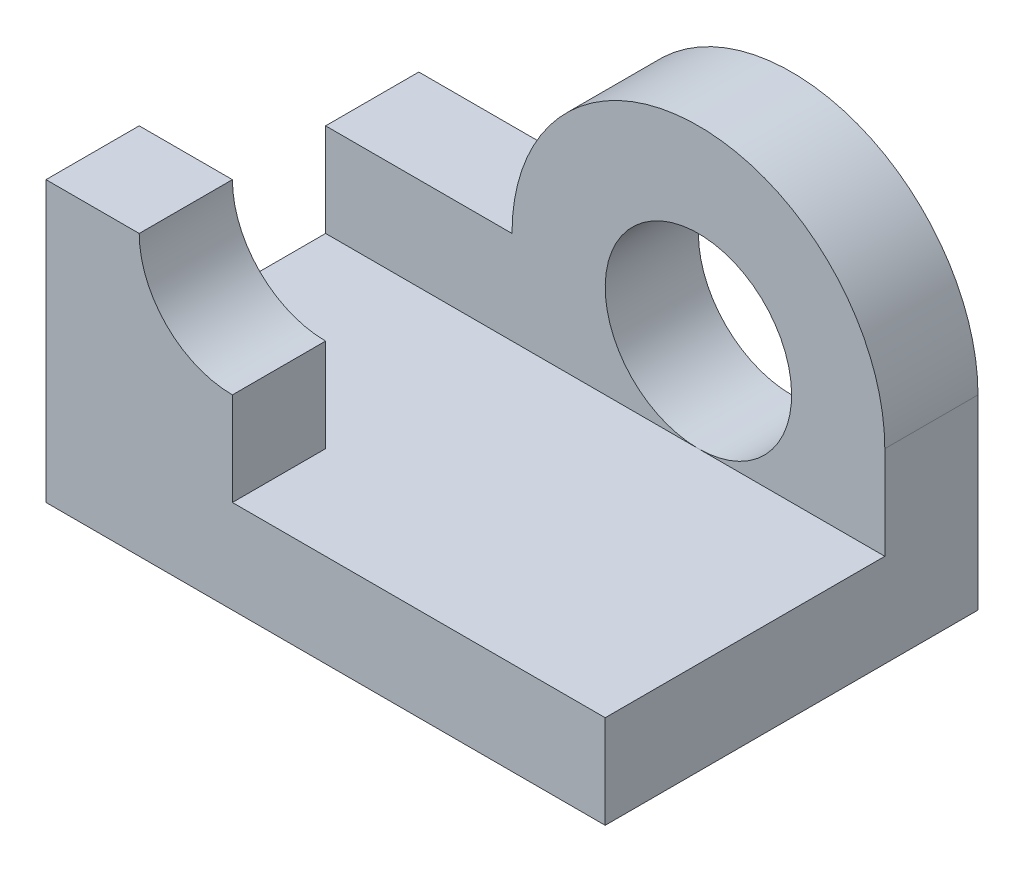
SolidWorks part; units mm, degrees
ref_plane "Front Plane" through (0, 0, 0) normal (0, 0, 1) x (1, 0, 0)
ref_plane "Top Plane" through (0, 0, 0) normal (0, 1, 0) x (1, 0, 0)
ref_plane "Right Plane" through (0, 0, 0) normal (1, 0, 0) x (0, 0, -1)
sketch "Sketch1" plane through (0, 0, 0) normal (0, 0, 1) x (1, 0, 0)
  line L0 (0, 0) -> (0, 762)
  line L1 (0, 762) -> (254, 762)
  line L2 (508, 508) -> (508, 254)
  line L3 (1524, 254) -> (1524, 508)
  line L4 (1524, 254) -> (508, 254)
  line L5 (1524, 254) -> (1524, 0)
  line L6 (1524, 0) -> (0, 0)
  line L7 (508, 508) -> (0, 508)
  line L8 (508, 254) -> (0, 254)
  arc A0 (254, 762) -> (508, 508) centre (508, 762) ccw
  arc A1 (1524, 508) -> (508, 508) centre (1016, 508) ccw
  circle A2 centre (1016, 508) radius 254
  dimension "D5" = 254
  dimension "D6" = 508
  dimension "D1" = 762
  dimension "D2" = 1524
  dimension "D3" = 254
  dimension "D4" = 254
extrude "Boss-Extrude3" add sketch "Sketch1" along normal blind 254 contours L4 A2 L3 A1 L2 | L4 L8 L0 L6 L5 | L8 L2 L7 L0 region at (762, 127, 0) region at (254, 381, 0) region at (520.7, 381, 0)
extrude "Boss-Extrude4" add sketch "Sketch1<8>" along normal blind 1016 contours L4 L8 L0 L6 L5 region at (762, 127, 0)
sketch "Sketch1<8>" plane through (0, 0, 0) normal (0, 0, 1) x (1, 0, 0) same geometry as "Sketch1"
extrude "Boss-Extrude5" add sketch "Sketch1<9>" along normal blind 254 from offset 762 contours A0 L1 L0 L7 | L8 L2 L7 L0 region at (254, 381, 0) region at (159.4633, 622.5853, 0)
sketch "Sketch1<9>" plane through (0, 0, 0) normal (0, 0, 1) x (1, 0, 0) same geometry as "Sketch1"
